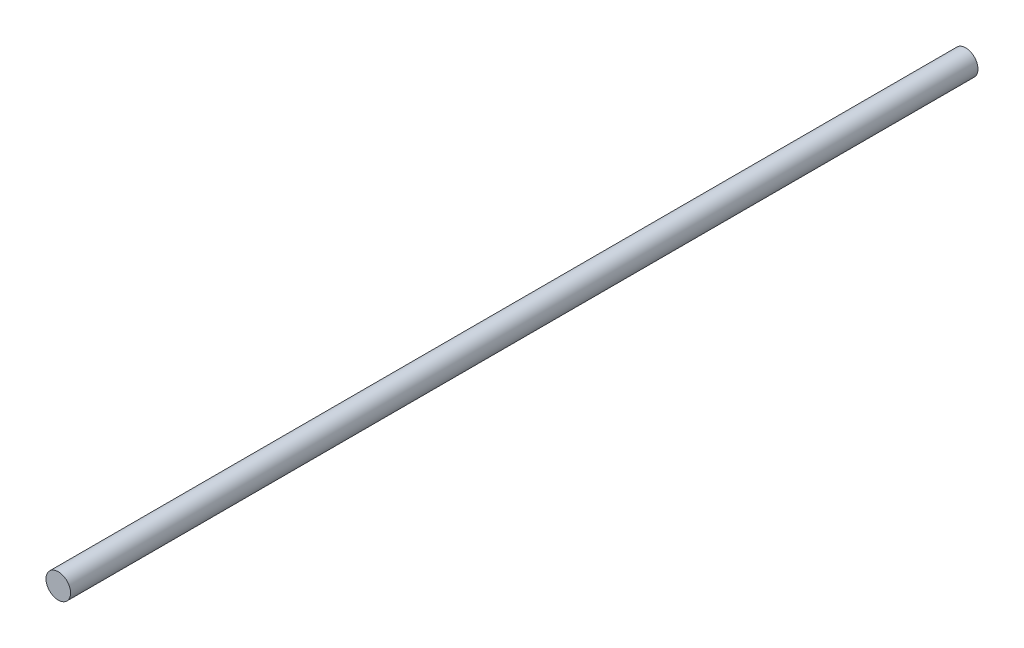
SolidWorks part; units mm, degrees
material "Plain Carbon Steel"
ref_plane "Спереди" through (0, 0, 0) normal (0, 0, 1) x (1, 0, 0)
ref_plane "Сверху" through (0, 0, 0) normal (0, 1, 0) x (1, 0, 0)
ref_plane "Справа" through (0, 0, 0) normal (1, 0, 0) x (0, 0, -1)
sketch "Sketch1" plane through (0, 0, 0) normal (0, 0, 1) x (1, 0, 0)
  circle A0 centre (0, 0) radius 4
  dimension "D1" = 8
extrude "Boss-Extrude1" add sketch "Sketch1" along normal blind 295
